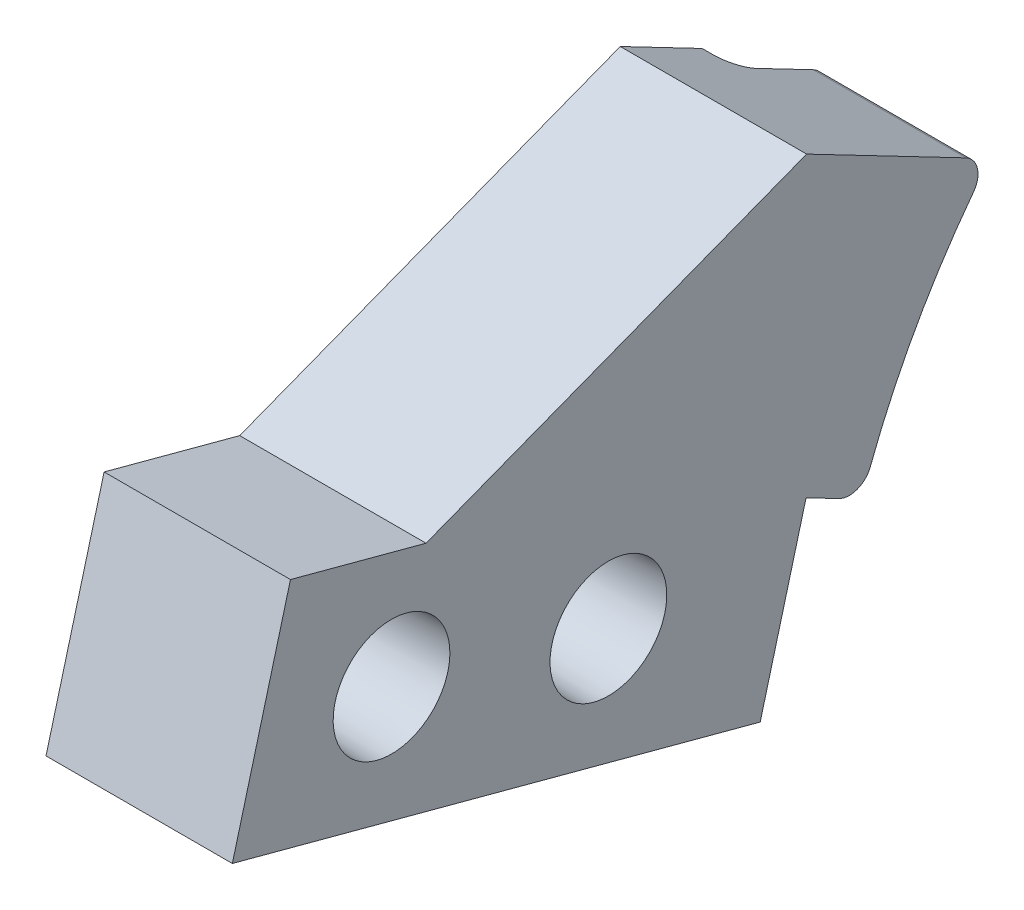
SolidWorks part; units mm, degrees
ref_plane "Front Plane" through (0, 0, 0) normal (0, 0, 1) x (1, 0, 0)
ref_plane "Top Plane" through (0, 0, 0) normal (0, 1, 0) x (1, 0, 0)
ref_plane "Right Plane" through (0, 0, 0) normal (1, 0, 0) x (0, 0, -1)
sketch "Sketch1" plane through (-13.45, 0, 0) normal (1, 0, 0) x (0, 0, -1)
  line L1 (-37.6711, 70.0939) -> (-61, 60) construction
  line L2 (-37.6711, 70.0939) -> (-61, 60) construction
  line L3 (-41.0809, 69.1634) -> (-34.1669, 72.1549)
  line L4 (-34.1669, 72.1549) -> (-32.7024, 71.3926)
  line L6 (-27.0474, 81.7075) -> (-32.951, 84.7807)
  line L11 (-33.1364, 70.2315) -> (-34.3363, 70.2468)
  line L12 (-28.0882, 82.2493) -> (-37.2866, 75.6323)
  line L13 (-37.5808, 75.887) -> (-32.951, 84.7807)
  line L14 (-32.951, 84.7807) -> (-34.1432, 85.4013)
  line L15 (-34.1432, 85.4013) -> (-51.0941, 78.867)
  line L16 (-51.0941, 78.867) -> (-57.1327, 80.485)
  line L17 (-57.1327, 80.485) -> (-59.7209, 70.8258)
  line L18 (-59.7209, 70.8258) -> (-45.8369, 67.1056)
  line L19 (-45.8369, 67.1056) -> (-41.0809, 69.1634)
  line L20 (-41.0809, 69.1634) -> (-39.4189, 72.3561)
  line L21 (-38.8128, 73.0562) -> (-27.3875, 81.2752)
  line L25 (-32.951, 84.7807) -> (-34.1432, 85.4013)
  line L26 (-34.1432, 85.4013) -> (-51.0941, 78.867)
  line L27 (-51.0941, 78.867) -> (-57.1327, 80.485)
  line L28 (-57.1327, 80.485) -> (-59.7209, 70.8258)
  line L29 (-59.7209, 70.8258) -> (-45.8369, 67.1056)
  line L30 (-45.8369, 67.1056) -> (-41.0809, 69.1634)
  arc A1 (36.4379, 53.575) -> (-35.7393, 69.5763) centre (0, 60) ccw construction
  arc A2 (36.4379, 53.575) -> (-35.7393, 69.5763) centre (0, 60) ccw construction
  arc A4 (-31.3062, 71.9237) -> (-26.7118, 80.217) centre (0, 60) cw
  arc A5 (-33.8074, 69.0587) -> (-26.9538, 80.5125) centre (-43.6146, 82.7043) ccw construction
  arc A6 (-32.7024, 71.3926) -> (-31.3062, 71.9237) centre (-32.2407, 72.2796) ccw
  arc A7 (-26.7118, 80.217) -> (-27.0474, 81.7075) centre (-27.5092, 80.8205) ccw
  arc A8 (-33.1364, 70.2315) -> (-32.3283, 69.8314) centre (-32.6365, 70.2252) ccw
  arc A9 (-34.3363, 70.2468) -> (-31.5887, 68.8865) centre (-32.6365, 70.2252) ccw
  arc A10 (-31.5887, 68.8865) -> (-25.3979, 80.7789) centre (-41.5711, 81.6405) ccw
  arc A11 (-25.3979, 80.7789) -> (-28.0882, 82.2493) centre (-27.0955, 80.8693) ccw
  arc A12 (-37.5808, 75.887) -> (-37.2866, 75.6323) centre (-37.4034, 75.7946) ccw
  arc A13 (-38.8128, 73.0562) -> (-39.4189, 72.3561) centre (-37.6448, 71.4326) ccw
  arc A14 (-26.5962, 80.8427) -> (-27.3875, 81.2752) centre (-27.0955, 80.8693) ccw
  arc A15 (-32.3283, 69.8314) -> (-26.5962, 80.8427) centre (-41.5711, 81.6405) ccw
  arc A24 (-30.4944, 83.5019) -> (-36.9038, 70.9707) centre (0, 60) ccw
  circle A27 centre (-42.972, 71.5143) radius 1.7
  circle A28 centre (-52.6312, 74.1025) radius 1.7
  circle A75 centre (-52.6312, 74.1025) radius 1.7 construction
  circle A76 centre (-42.972, 71.5143) radius 1.7 construction
  point P42 (-31.6891, 70.8651)
  dimension "D2" = 1
  dimension "D3" = 5
  dimension "D4" = 3.5
  dimension "D1" = 0
extrude "Boss-Extrude1" add sketch "Sketch1" along normal up to surface (1.5 mm away) region at (-13.45, 72.1267, 38.0279) region at (-13.45, 75.6746, 46.4185) region at (-13.45, 80.5263, 33.9352)
extrude "Boss-Extrude2" add sketch "Sketch1<3>" along normal blind 1.5 from surface contours A28 | A27 | L6 L25 L26 L27 L28 L29 L30 L3 L4 A6 A4 A7 region at (-13.45, 71.5143, 42.972) region at (-13.45, 74.1025, 52.6312) starting at face at (-11.95, 73.2143, 42.972)
sketch "Sketch1<3>" plane through (-13.45, 0, 0) normal (1, 0, 0) x (0, 0, -1) same geometry as "Sketch1"
fillet "Fillet1" radius 1 1 edges at (-11.95, 77.5317, 34.2767)
sketch "Sketch2" plane through (-10.45, 0, 0) normal (1, 0, 0) x (0, 0, -1)
  line L0 (-34.1669, 72.1549) -> (-36.211, 64.5263)
  line L1 (-36.211, 64.5263) -> (-45.8369, 67.1056)
  line L5 (-45.8369, 67.1056) -> (-59.7209, 70.8258) construction
  line L38 (-27.0474, 81.7075) -> (-34.1432, 85.4013)
  line L39 (-34.1432, 85.4013) -> (-51.0941, 78.867)
  line L40 (-51.0941, 78.867) -> (-57.1327, 80.485)
  line L41 (-57.1327, 80.485) -> (-59.7209, 70.8258)
  line L42 (-59.7209, 70.8258) -> (-45.8369, 67.1056)
  line L43 (-45.8369, 67.1056) -> (-34.1669, 72.1549)
  line L44 (-34.1669, 72.1549) -> (-32.7024, 71.3926)
  line L45 (-27.0474, 81.7075) -> (-34.1432, 85.4013)
  line L46 (-34.1432, 85.4013) -> (-51.0941, 78.867)
  line L47 (-51.0941, 78.867) -> (-57.1327, 80.485)
  line L48 (-57.1327, 80.485) -> (-59.7209, 70.8258)
  line L49 (-59.7209, 70.8258) -> (-45.8369, 67.1056)
  line L51 (-34.1669, 72.1549) -> (-32.7024, 71.3926)
  circle A0 centre (-52.6312, 74.1025) radius 1.7 construction
  circle A1 centre (-42.972, 71.5143) radius 1.7 construction
  circle A12 centre (-42.972, 71.5143) radius 1.7
  circle A13 centre (-52.6312, 74.1025) radius 1.7
  arc A15 (-32.7024, 71.3926) -> (-31.3062, 71.9237) centre (-32.2407, 72.2796) ccw
  arc A16 (-26.7118, 80.217) -> (-31.3062, 71.9237) centre (0, 60) ccw
  arc A23 (-26.7118, 80.217) -> (-27.0474, 81.7075) centre (-27.5092, 80.8205) ccw
  arc A24 (-32.7024, 71.3926) -> (-31.3062, 71.9237) centre (-32.2407, 72.2796) ccw
  arc A25 (-26.7118, 80.217) -> (-31.3062, 71.9237) centre (0, 60) ccw
  arc A26 (-26.7118, 80.217) -> (-27.0474, 81.7075) centre (-27.5092, 80.8205) ccw
  point P2 (-35.712, 64.9379)
  dimension "D1" = 0
extrude "Boss-Extrude3" add sketch "Sketch2" along normal blind 5.3
sketch "Sketch3" plane through (-5.15, 0, 0) normal (1, 0, 0) x (0, 0, -1)
  circle A0 centre (-42.972, 71.5143) radius 1.7 construction
  circle A1 centre (-52.6312, 74.1025) radius 1.7 construction
  circle A2 centre (-42.972, 71.5143) radius 1.7 construction
  circle A3 centre (-52.6312, 74.1025) radius 1.7 construction
  circle A4 centre (-52.6312, 74.1025) radius 2.6
  circle A5 centre (-42.972, 71.5143) radius 2.6
  dimension "D1" = 5.2
  dimension "D2" = 5.2
extrude "Cut-Extrude1" cut sketch "Sketch3" against normal blind 3.9 draft 1.5
equation "\"D2@Sketch3\"=\"D1@Sketch3\""
